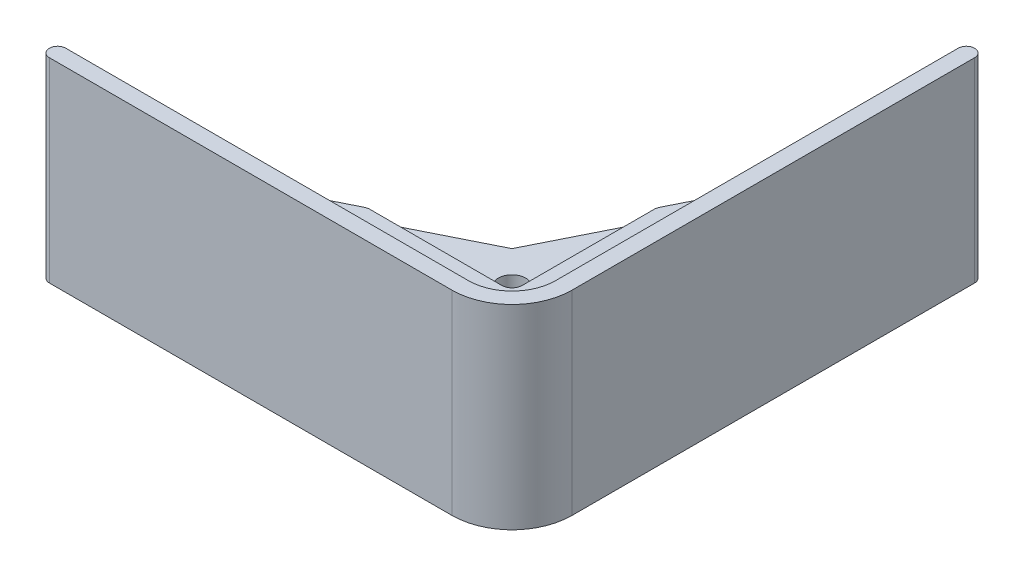
SolidWorks part; units mm, degrees
material "Nylon 101"
ref_plane "Front Plane" through (0, 0, 0) normal (0, 0, 1) x (1, 0, 0)
ref_plane "Top Plane" through (0, 0, 0) normal (0, 1, 0) x (1, 0, 0)
ref_plane "Right Plane" through (0, 0, 0) normal (1, 0, 0) x (0, 0, -1)
sketch "Sketch1" plane through (0, 0, 0) normal (0, 1, 0) x (1, 0, 0)
  line L0 (0, -18.542) -> (-127, -18.542)
  line L1 (18.542, 0) -> (18.542, 127)
  line L2 (-127, -18.542) -> (-127, -13.462)
  line L3 (-127, -13.462) -> (0, -13.462)
  line L4 (13.462, 0) -> (13.462, 127)
  line L5 (13.462, 127) -> (18.542, 127)
  line L6 (-6.0067, 12.0476) -> (-57.1711, -13.462)
  line L7 (-12.0476, 6.0067) -> (13.462, 57.1711)
  circle A0 centre (0, 0) radius 4.2862
  arc A1 (0, -18.542) -> (18.542, 0) centre (0, 0) ccw
  circle A2 centre (0, 0) radius 13.462
  dimension "D1" = 8.5725
  dimension "D4" = 5.08
  dimension "D5" = 127
  dimension "D6" = 26.5
  dimension "D3" = 13.462
extrude "Boss-Extrude1" add sketch "Sketch1" along normal blind 50.8 contours A2 L3 L2 L0 A1 L1 L5 L4 | A2 A0 | A2 L3 | A2 L4 L7 | A2 L6 L7 region at (-63.5, 0, 16.4837) region at (-26.4429, 0, 6.2746) region at (-11.1237, 0, 6.8835) region at (6.2746, 0, -26.4429) region at (-9.6262, 0, -9.6262)
fillet "Fillet2" radius 2.54 4 edges at (13.462, 25.4, -127) (18.542, 25.4, -127) (-127, 25.4, 13.462) (-127, 25.4, 18.542)
ref_plane "Plane1" through (0, 25.4, 0) normal (0, 1, 0) x (1, 0, 0)
sketch "Sketch7" plane through (0, 50.8, 0) normal (0, 1, 0) x (1, 0, 0)
  line L1 (4.826, -4.826) -> (-39.8499, -4.826)
  line L2 (4.826, -4.826) -> (4.826, 39.8499)
  line L3 (4.826, 39.8499) -> (-39.8499, 39.8499)
  line L4 (-39.8499, -4.826) -> (-39.8499, 39.8499)
  line L6 (-10.0378, 10.0378) -> (-57.1711, -13.462) construction
  circle A1 centre (0, 0) radius 4.2862 construction
  dimension "D1" = 4.826
  dimension "D2" = 4.826
extrude "Cut-Extrude3" cut sketch "Sketch7" against normal blind 3.429
fillet "Fillet9" radius 3.175 3 edges at (4.826, 49.0855, -39.8499) (4.826, 49.0855, 4.826) (-39.8499, 49.0855, 4.826)
sketch "Sketch8" plane through (0, 25.4, 0) normal (0, 1, 0) x (1, 0, 0)
  line L0 (0, -13.462) -> (-124.46, -13.462)
  line L10 (13.462, 57.1711) -> (5.1596, 40.519)
  line L11 (4.826, 39.1023) -> (4.826, -1.651)
  line L12 (1.651, -4.826) -> (-39.1023, -4.826)
  line L13 (-40.519, -5.1596) -> (-57.1711, -13.462)
  line L14 (-57.1711, -13.462) -> (-124.46, -13.462)
  line L16 (-124.46, -18.542) -> (0, -18.542)
  line L17 (18.542, 0) -> (18.542, 124.46)
  line L19 (13.462, 124.46) -> (13.462, 57.1711)
  line L26 (-124.46, -18.542) -> (0, -18.542)
  line L27 (18.542, 0) -> (18.542, 124.46)
  line L29 (13.462, 124.46) -> (13.462, 0)
  arc A0 (0, -13.462) -> (13.462, 0) centre (0, 0) ccw
  arc A9 (5.1596, 40.519) -> (4.826, 39.1023) centre (8.001, 39.1023) ccw
  arc A10 (1.651, -4.826) -> (4.826, -1.651) centre (1.651, -1.651) ccw
  arc A11 (-39.1023, -4.826) -> (-40.519, -5.1596) centre (-39.1023, -8.001) ccw
  arc A12 (-124.46, -13.462) -> (-127, -16.002) centre (-124.46, -16.002) ccw
  arc A13 (-127, -16.002) -> (-124.46, -18.542) centre (-124.46, -16.002) ccw
  arc A14 (0, -18.542) -> (18.542, 0) centre (0, 0) ccw
  arc A15 (18.542, 124.46) -> (16.002, 127) centre (16.002, 124.46) ccw
  arc A16 (16.002, 127) -> (13.462, 124.46) centre (16.002, 124.46) ccw
  arc A21 (-124.46, -13.462) -> (-127, -16.002) centre (-124.46, -16.002) ccw
  arc A22 (-127, -16.002) -> (-124.46, -18.542) centre (-124.46, -16.002) ccw
  arc A23 (0, -18.542) -> (18.542, 0) centre (0, 0) ccw
  arc A24 (18.542, 124.46) -> (16.002, 127) centre (16.002, 124.46) ccw
  arc A25 (16.002, 127) -> (13.462, 124.46) centre (16.002, 124.46) ccw
  dimension "D1" = 0
extrude "Boss-Extrude2" add sketch "Sketch8" along normal mid plane 60.325
sketch "Sketch9" plane through (0, -4.7625, 0) normal (0, -1, 0) x (1, 0, 0)
  line L0 (-8.2875, 13.462) -> (7.112, 13.462)
  line L1 (-57.1711, 13.462) -> (0, 13.462) construction
  line L2 (13.462, -7.7751) -> (13.462, 7.112)
  line L3 (13.462, 0) -> (13.462, -57.1711) construction
  arc A0 (7.112, 13.462) -> (13.462, 7.112) centre (7.112, 7.112) cw
  arc A1 (13.462, 0) -> (0, 13.462) centre (0, 0) ccw construction
  arc A2 (13.462, 0) -> (0, 13.462) centre (0, 0) ccw
  point P9 (8.6874, 8.6874)
  arc M4 (0, 13.462) -> (13.462, 0) centre (0, 0) cw
  dimension "D1" = 6.35
extrude "Cut-Extrude4" cut sketch "Sketch9" along direction (0, 1, 0) on the side against the normal blind 4.7625 contours A0 L0 L2 M4 region at (10.0004, -4.7625, 10.0004)
equation "\"D1@Sketch1\"=.3125+0.025"
